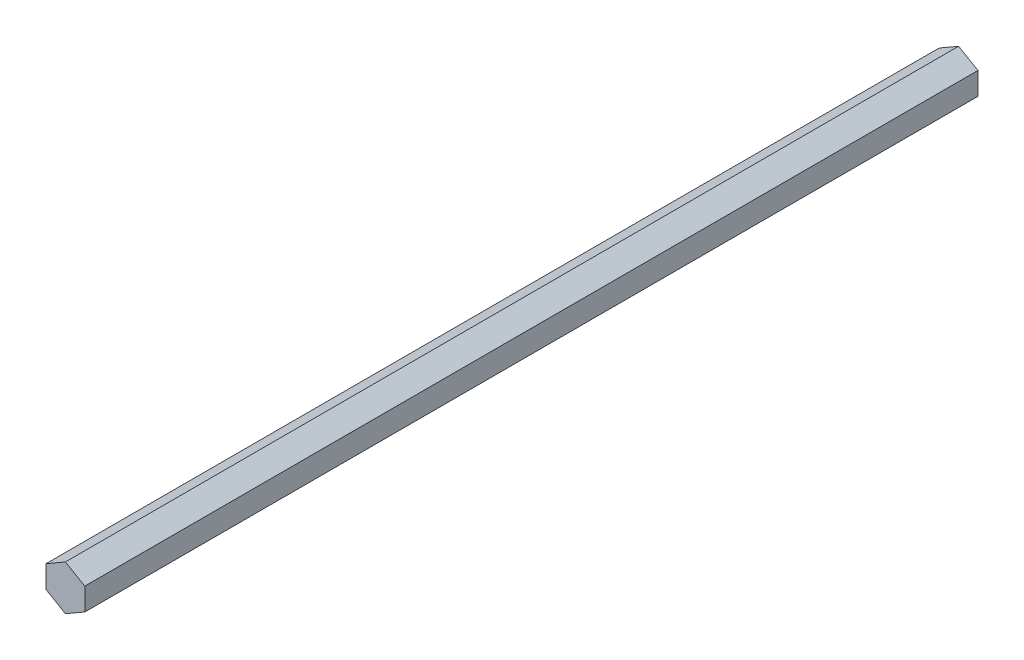
SolidWorks part; units mm, degrees
ref_plane "Front Plane" through (0, 0, 0) normal (0, 0, 1) x (1, 0, 0)
ref_plane "Top Plane" through (0, 0, 0) normal (0, 1, 0) x (1, 0, 0)
ref_plane "Right Plane" through (0, 0, 0) normal (1, 0, 0) x (0, 0, -1)
sketch "Sketch1" plane through (0, 0, 0) normal (0, 0, 1) x (1, 0, 0)
  line L0 (0, 0) -> (0, 7.3323) construction
  line L7 (6.35, 3.6662) -> (0, 7.3323)
  line L8 (0, 7.3323) -> (-6.35, 3.6662)
  line L9 (-6.35, 3.6662) -> (-6.35, -3.6662)
  line L10 (-6.35, -3.6662) -> (0, -7.3323)
  line L11 (0, -7.3323) -> (6.35, -3.6662)
  line L12 (6.35, -3.6662) -> (6.35, 3.6662)
  circle A1 centre (0, 0) radius 6.35 construction
  dimension "D1" = 12.7
extrude "Boss-Extrude1" add sketch "Sketch1" along normal blind 292.1
ref_axis "Axis1" through (0, 0, 306.705) along (0, 0, -1)
